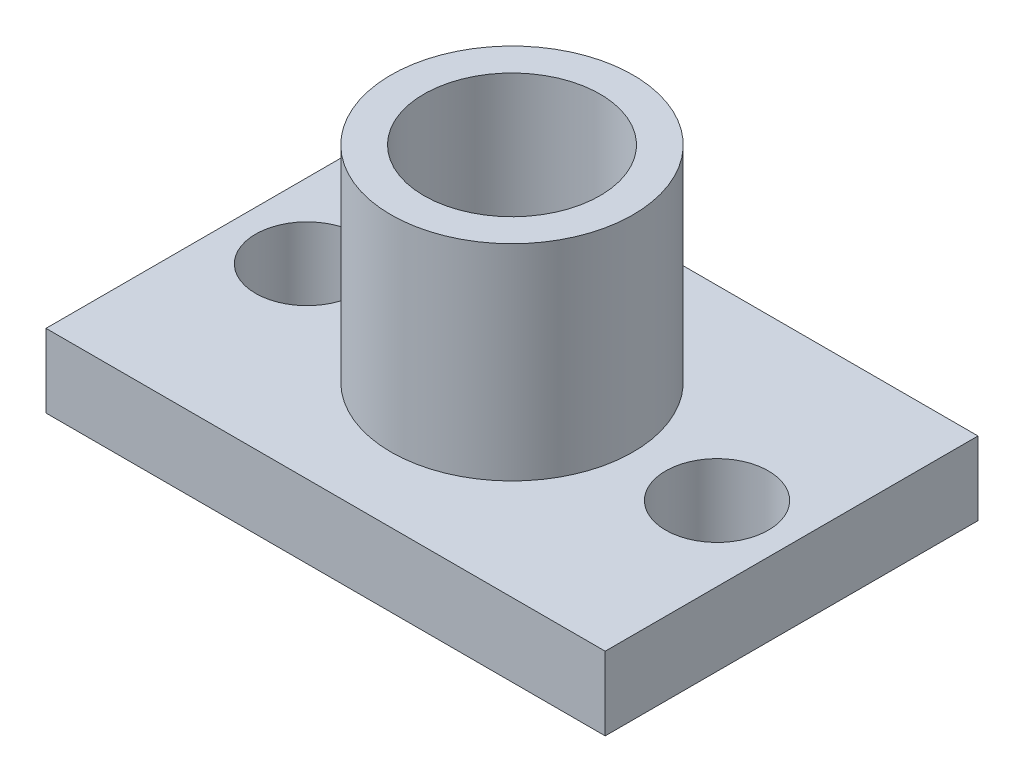
SolidWorks part; units mm, degrees
ref_plane "前视" through (0, 0, 0) normal (0, 0, 1) x (1, 0, 0)
ref_plane "上视" through (0, 0, 0) normal (0, 1, 0) x (1, 0, 0)
ref_plane "右视" through (0, 0, 0) normal (1, 0, 0) x (0, 0, -1)
sketch "Sketch1" plane through (0, 0, 0) normal (0, 1, 0) x (1, 0, 0)
  line L1 (-25.8417, 12.7) -> (12.2583, 12.7)
  line L2 (-25.8417, 12.7) -> (-25.8417, -12.7)
  line L3 (-25.8417, -12.7) -> (12.2583, -12.7)
  line L4 (12.2583, 12.7) -> (12.2583, -12.7)
  dimension "D1" = 25.4
  dimension "D2" = 38.1
extrude "Boss-Extrude1" add sketch "Sketch1" along normal blind 5
ref_point "Point1"
sketch "Sketch3" plane through (0, 5, 0) normal (0, 1, 0) x (1, 0, 0)
  circle A0 centre (-6.7917, 0) radius 8.25
  circle A1 centre (-6.7917, 0) radius 6
  dimension "D1" = 16.5
  dimension "D2" = 12
extrude "Boss-Extrude2" add sketch "Sketch3" along normal blind 14
ref_axis "Axis1" through (12.2583, 5, 0) along (-1, 0, 0)
sketch "Sketch4" plane through (0, 5, 0) normal (0, 1, 0) x (1, 0, 0)
  line L0 (12.2583, -12.7) -> (12.2583, 12.7) construction
  line L1 (-25.8417, 12.7) -> (-25.8417, -12.7) construction
  circle A0 centre (7.1783, 0) radius 3.5
  circle A1 centre (-20.7617, 0) radius 3.5
  point P0 (7.1783, 0)
  point P1 (12.2583, 0)
  point P4 (-20.7617, 0)
  dimension "D3" = 7
  dimension "D4" = 7
  dimension "D1" = 5.08
  dimension "D2" = 5.08
extrude "Cut-Extrude1" cut sketch "Sketch4" against normal through all
sketch "Sketch5" plane through (0, 5, 0) normal (0, 1, 0) x (1, 0, 0)
  line L0 (-6.7917, 0) -> (-6.7917, -6.4335) construction
  line L1 (-17.3636, 4.5849) -> (-15.7636, 4.5849)
  line L2 (-17.3636, 4.5849) -> (-17.3636, -5.4151)
  line L3 (-17.3636, -5.4151) -> (-15.7636, -5.4151)
  line L4 (-15.7636, 4.5849) -> (-15.7636, -5.4151)
  line L5 (3.7802, -5.4151) -> (2.1802, -5.4151)
  line L6 (2.1802, 4.5849) -> (2.1802, -5.4151)
  line L7 (3.7802, 4.5849) -> (3.7802, -5.4151)
  line L8 (3.7802, 4.5849) -> (2.1802, 4.5849)
  dimension "D1" = 1.6
  dimension "D2" = 10
